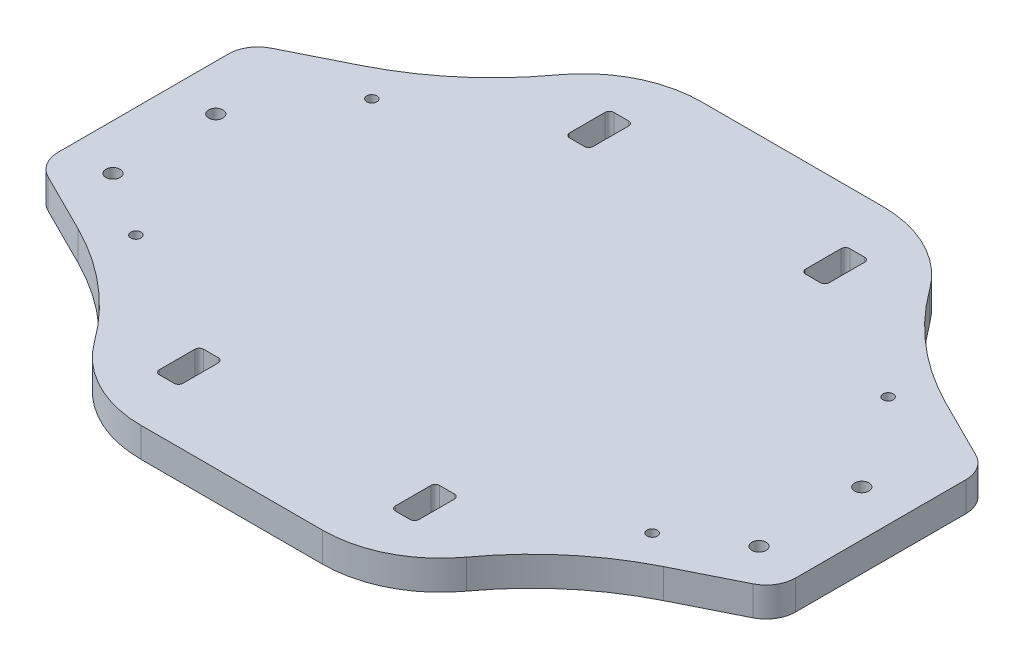
SolidWorks part; units mm, degrees
ref_plane "Front Plane" through (0, 0, 0) normal (0, 0, 1) x (1, 0, 0)
ref_plane "Top Plane" through (0, 0, 0) normal (0, 1, 0) x (1, 0, 0)
ref_plane "Right Plane" through (0, 0, 0) normal (1, 0, 0) x (0, 0, -1)
sketch "Sketch2" plane through (0, 0, 0) normal (0, 1, 0) x (1, 0, 0)
  line L0 (-125, 35.0363) -> (-11.1726, 91.9008)
  line L1 (36, -62.0363) -> (44, -77.0363) construction
  line L2 (-125, -35.0363) -> (-125, 35.0363)
  line L3 (-125, 35.0363) -> (125, 35.0363)
  line L4 (125, -35.0363) -> (125, 35.0363)
  line L5 (0, 0) -> (125, 35.0363) construction
  line L6 (-125, 35.0363) -> (0, 0) construction
  line L7 (-44, 77.0363) -> (-36, 77.0363)
  line L8 (-44, 77.0363) -> (-44, 62.0363)
  line L9 (-44, 62.0363) -> (-36, 62.0363)
  line L10 (-36, 77.0363) -> (-36, 62.0363)
  line L11 (125, 35.0363) -> (11.1726, 91.9008)
  line L12 (-40, 69.5363) -> (40, 69.5363)
  line L13 (-40, 62.0363) -> (-40, 77.0363) construction
  line L14 (125, 0) -> (-125, 0) construction
  line L15 (36, 77.0363) -> (44, 77.0363)
  line L16 (36, 77.0363) -> (36, 62.0363)
  line L17 (36, 62.0363) -> (44, 62.0363)
  line L18 (44, 77.0363) -> (44, 62.0363)
  line L19 (36, 77.0363) -> (44, 62.0363) construction
  line L20 (36, 62.0363) -> (44, 77.0363) construction
  line L21 (36, -77.0363) -> (44, -62.0363) construction
  line L22 (-40, -62.0363) -> (-40, -77.0363) construction
  line L23 (-125, -35.0363) -> (0, 0) construction
  line L24 (0, 0) -> (125, -35.0363) construction
  line L25 (44, -77.0363) -> (44, -62.0363)
  line L26 (36, -62.0363) -> (44, -62.0363)
  line L27 (36, -77.0363) -> (36, -62.0363)
  line L28 (36, -77.0363) -> (44, -77.0363)
  line L29 (-40, -69.5363) -> (40, -69.5363)
  line L30 (125, -35.0363) -> (11.1726, -91.9008)
  line L31 (-36, -77.0363) -> (-36, -62.0363)
  line L32 (-44, -62.0363) -> (-36, -62.0363)
  line L33 (-44, -77.0363) -> (-44, -62.0363)
  line L34 (-44, -77.0363) -> (-36, -77.0363)
  line L35 (-125, -35.0363) -> (125, -35.0363)
  line L36 (-125, -35.0363) -> (-11.1726, -91.9008)
  line L37 (-70, 95) -> (70, -95) construction
  line L38 (-109.5, -23.3363) -> (-109.5, 6.6637) construction
  line L39 (-70, 95) -> (70, 95)
  line L40 (0, 40) -> (0, -40) construction
  line L41 (-70, 95) -> (-70, -95)
  line L42 (-70, -95) -> (70, -95)
  line L43 (70, 95) -> (70, -95)
  line L44 (-70, -95) -> (70, 95) construction
  line L45 (0, -40) -> (-175, -40) construction
  line L46 (0, 40) -> (-175, 40) construction
  line L47 (-87.5, -40) -> (-87.5, 40) construction
  circle A0 centre (0, 69.5363) radius 25
  circle A1 centre (0, -69.5363) radius 25
  circle A2 centre (-109.5, -25.7613) radius 2.425
  circle A3 centre (-109.5, 9.0887) radius 2.425
  circle A4 centre (109.5, 9.0887) radius 2.425
  circle A5 centre (109.5, -25.7613) radius 2.425
  circle A6 centre (-87.5, -40) radius 1.75
  circle A7 centre (-87.5, 40) radius 1.75
  circle A8 centre (87.5, 40) radius 1.75
  circle A9 centre (87.5, -40) radius 1.75
  point P0 (0, 0)
  point P16 (0, 69.5363)
  point P19 (-40, 69.5363)
  point P31 (0, 0)
  point P44 (0, 0)
  point P55 (0, 0)
  dimension "D3" = 8
  dimension "D9" = 50
  dimension "D2" = 4.85
  dimension "D10" = 4.85
  dimension "D11" = 30
  dimension "D14" = 140
  dimension "D18" = 175
  dimension "D4" = 80
  dimension "D5" = 27
  dimension "D6" = 8
  dimension "D7" = 15
  dimension "D8" = 15
  dimension "D12" = 250
  dimension "D13" = 15.5
  dimension "D15" = 34.85
  dimension "D16" = 190
  dimension "D17" = 80
extrude "Boss-Extrude1" add sketch "Sketch2" along normal blind 10
fillet "Fillet1" radius 10 4 edges at (125, 5, -35.0363) (125, 5, 35.0363) (-125, 5, -35.0363) (-125, 5, 35.0363)
fillet "Fillet2" radius 40 4 edges at (-70, 5, 95) (70, 5, 95) (70, 5, -95) (-70, 5, -95)
fillet "Fillet4" radius 1.5 16 edges at (-44, 5, -62.0363) (36, 5, -62.0363) (36, 5, -77.0363) (-44, 5, -77.0363) (44, 5, -77.0363) (-36, 5, -77.0363) (44, 5, -62.0363) (-36, 5, -62.0363) (44, 5, 77.0363) (44, 5, 62.0363) (36, 5, 62.0363) (36, 5, 77.0363) (-44, 5, 77.0363) (-36, 5, 77.0363) (-36, 5, 62.0363) (-44, 5, 62.0363)
fillet "Fillet3" radius 100 4 edges at (-70, 5, -62.5126) (70, 5, -62.5126) (-70, 5, 62.5126) (70, 5, 62.5126)
sketch "Sketch3" plane through (0, 10, 0) normal (0, 1, 0) x (1, 0, 0)
  line L0 (0, 35) -> (0, -35)
  line L1 (-125, 35) -> (125, 35)
  line L2 (-125, 35) -> (-125, -35)
  line L3 (-125, -35) -> (125, -35)
  line L4 (125, 35) -> (125, -35)
  point P0 (0, 0)
  dimension "D1" = 70
  dimension "D2" = 250
